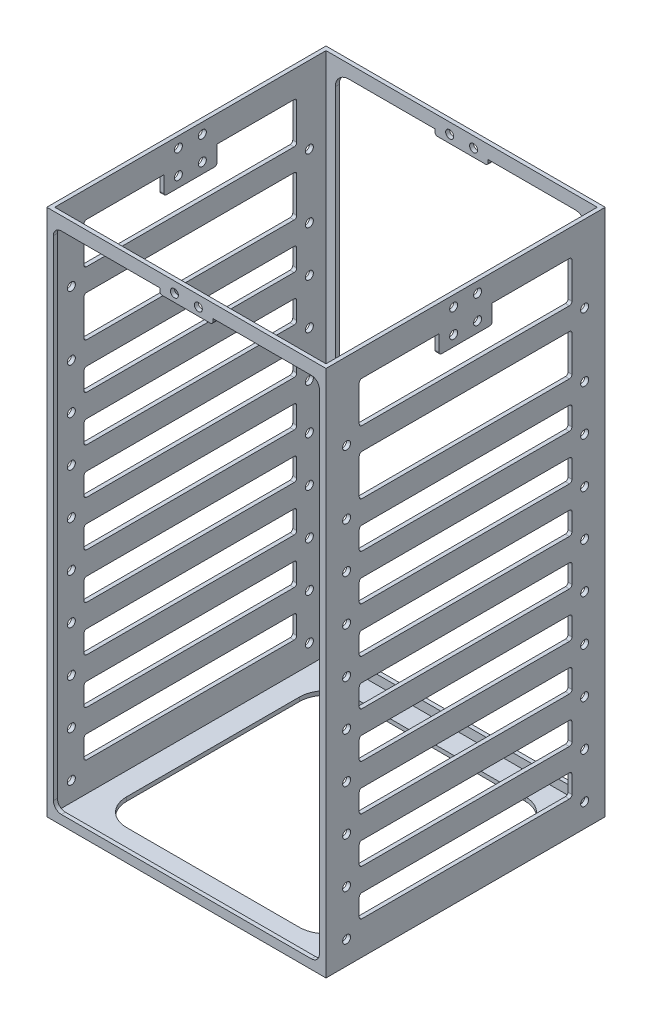
SolidWorks part; units mm, degrees
ref_plane "Front Plane" through (0, 0, 0) normal (0, 0, 1) x (1, 0, 0)
ref_plane "Top Plane" through (0, 0, 0) normal (0, 1, 0) x (1, 0, 0)
ref_plane "Right Plane" through (0, 0, 0) normal (1, 0, 0) x (0, 0, -1)
sketch "Sketch1" plane through (0, 0, 0) normal (0, 1, 0) x (1, 0, 0)
  line L1 (-52.5, -52.5) -> (52.5, -52.5)
  line L2 (-52.5, -52.5) -> (-52.5, 52.5)
  line L3 (-52.5, 52.5) -> (52.5, 52.5)
  line L4 (52.5, -52.5) -> (52.5, 52.5)
  line L5 (-52.5, -52.5) -> (52.5, 52.5) construction
  line L6 (-52.5, 52.5) -> (52.5, -52.5) construction
  line L7 (-32.5, -42.5) -> (32.5, -42.5)
  line L8 (-42.5, -32.5) -> (-42.5, 32.5)
  line L9 (-32.5, 42.5) -> (32.5, 42.5)
  line L10 (42.5, -32.5) -> (42.5, 32.5)
  line L11 (-42.5, -42.5) -> (42.5, 42.5) construction
  line L12 (-42.5, 42.5) -> (42.5, -42.5) construction
  arc A0 (32.5, -42.5) -> (42.5, -32.5) centre (32.5, -32.5) ccw
  arc A1 (32.5, 42.5) -> (42.5, 32.5) centre (32.5, 32.5) cw
  arc A2 (-42.5, 32.5) -> (-32.5, 42.5) centre (-32.5, 32.5) cw
  arc A3 (-32.5, -42.5) -> (-42.5, -32.5) centre (-32.5, -32.5) cw
  point P0 (0, 0)
  point P6 (0, 0)
  dimension "D3" = 10
  dimension "D1" = 105
  dimension "D2" = 42.5
extrude "Boss-Extrude2" add sketch "Sketch1" along normal blind 1.5 contours A3 L7 A0 L10 A1 L9 A2 L8 | L2 L1 L4 L3 region at (0, 0, 0)
sketch "Sketch3" plane through (0, 1.5, 0) normal (0, 1, 0) x (1, 0, 0)
  line L1 (-52.5, -52.5) -> (52.5, -52.5)
  line L2 (-52.5, -52.5) -> (-52.5, 52.5)
  line L3 (-52.5, 52.5) -> (52.5, 52.5)
  line L4 (52.5, -52.5) -> (52.5, 52.5)
  line L5 (-52.5, -52.5) -> (52.5, 52.5) construction
  line L6 (-52.5, 52.5) -> (52.5, -52.5) construction
  line L7 (-51, -51) -> (51, -51)
  line L8 (-51, -51) -> (-51, 51)
  line L9 (-51, 51) -> (51, 51)
  line L10 (51, -51) -> (51, 51)
  line L11 (-51, -51) -> (51, 51) construction
  line L12 (-51, 51) -> (51, -51) construction
  point P0 (0, 0)
  point P7 (0, 0)
  dimension "D1" = 1.5
extrude "Boss-Extrude3" add sketch "Sketch3" along normal blind 197 contours L8 L7 L10 L9 | L2 L3 L4 L1
sketch "Sketch4" plane through (0, 0, -52.5) normal (0, 0, 1) x (1, 0, 0)
  line L0 (-52.5, 0) -> (52.5, 0) construction
  line L1 (-42.5, 5) -> (42.5, 5)
  line L2 (-47.5, 10) -> (-47.5, 188.5)
  line L3 (-42.5, 193.5) -> (42.5, 193.5)
  line L4 (47.5, 10) -> (47.5, 188.5)
  line L5 (-47.5, 5) -> (47.5, 193.5) construction
  line L6 (-47.5, 193.5) -> (47.5, 5) construction
  line L7 (52.5, 198.5) -> (52.5, 0) construction
  line L8 (-51, 198.5) -> (51, 198.5) construction
  line L9 (-52.5, 198.5) -> (-52.5, 0) construction
  arc A0 (-42.5, 5) -> (-47.5, 10) centre (-42.5, 10) cw
  arc A1 (42.5, 5) -> (47.5, 10) centre (42.5, 10) ccw
  arc A2 (42.5, 193.5) -> (47.5, 188.5) centre (42.5, 188.5) cw
  arc A3 (-47.5, 188.5) -> (-42.5, 193.5) centre (-42.5, 188.5) cw
  point P0 (0, 99.25)
  dimension "D5" = 5
  dimension "D1" = 5
  dimension "D2" = 5
  dimension "D3" = 5
  dimension "D4" = 5
extrude "Cut-Extrude1" cut sketch "Sketch4" along normal up to surface (1.5 mm away) up to face at (0, 100, -51)
sketch "Sketch5" plane through (0, 0, 52.5) normal (0, 0, 1) x (1, 0, 0)
  line L0 (-52.5, 198.5) -> (52.5, 198.5) construction
  line L1 (-47, 3.5) -> (47, 3.5)
  line L2 (-50, 6.5) -> (-50, 190.5)
  line L3 (-47, 193.5) -> (47, 193.5)
  line L4 (50, 6.5) -> (50, 190.5)
  line L5 (-50, 3.5) -> (50, 193.5) construction
  line L6 (-50, 193.5) -> (50, 3.5) construction
  line L7 (-52.5, 1.5) -> (52.5, 1.5) construction
  line L8 (-52.5, 198.5) -> (-52.5, 0) construction
  line L9 (52.5, 198.5) -> (52.5, 0) construction
  arc A0 (47, 3.5) -> (50, 6.5) centre (47, 6.5) ccw
  arc A1 (-47, 3.5) -> (-50, 6.5) centre (-47, 6.5) cw
  arc A2 (47, 193.5) -> (50, 190.5) centre (47, 190.5) cw
  arc A3 (-50, 190.5) -> (-47, 193.5) centre (-47, 190.5) cw
  point P0 (0, 98.5)
  dimension "D5" = 3
  dimension "D1" = 5
  dimension "D2" = 2
  dimension "D3" = 2.5
  dimension "D4" = 2.5
sketch "Sketch6" plane through (52.5, 0, 0) normal (1, 0, 0) x (0, 0, -1)
  line L0 (-52.5, 3.5) -> (-52.5, 193.5) construction
  line L1 (52.5, 198.5) -> (52.5, 0) construction
  line L2 (-52.5, 0) -> (52.5, 0) construction
  circle A0 centre (-44.75, 8.75) radius 1.5
  circle A1 centre (44.75, 8.75) radius 1.5
  circle A2 centre (-44.75, 25.85) radius 1.5
  circle A3 centre (44.75, 25.85) radius 1.5
  circle A4 centre (-44.75, 42.95) radius 1.5
  circle A5 centre (44.75, 42.95) radius 1.5
  circle A6 centre (-44.75, 60.05) radius 1.5
  circle A7 centre (44.75, 60.05) radius 1.5
  circle A8 centre (-44.75, 77.15) radius 1.5
  circle A9 centre (44.75, 77.15) radius 1.5
  circle A10 centre (-44.75, 94.25) radius 1.5
  circle A11 centre (44.75, 94.25) radius 1.5
  circle A12 centre (-44.75, 111.35) radius 1.5
  circle A13 centre (44.75, 111.35) radius 1.5
  circle A14 centre (-44.75, 128.45) radius 1.5
  circle A15 centre (44.75, 128.45) radius 1.5
  circle A16 centre (-44.75, 145.55) radius 1.5
  circle A17 centre (44.75, 145.55) radius 1.5
  circle A18 centre (-44.75, 169.55) radius 1.5
  circle A19 centre (44.75, 169.55) radius 1.5
  dimension "D4" = 3
  dimension "D5" = 3
  dimension "D1" = 7.75
  dimension "D2" = 7.75
  dimension "D3" = 8.75
  dimension "D7" = 17.1
  dimension "D9" = 24
  dimension "D6" = 9
  dimension "D8" = 2
extrude "Cut-Extrude2" cut sketch "Sketch6" against normal through all
extrude "Cut-Extrude3" cut sketch "Sketch5" against normal up to surface (1.5 mm away) up to face at (0, 100, 51)
sketch "Sketch7" plane through (52.5, 0, 0) normal (1, 0, 0) x (0, 0, -1)
  line L0 (-40, 30.65) -> (-40, 37.15)
  line L1 (-39, 12.55) -> (39, 12.55)
  line L2 (-40, 13.55) -> (-40, 20.05)
  line L3 (-39, 21.05) -> (39, 21.05)
  line L4 (40, 13.55) -> (40, 20.05)
  line L5 (-40, 12.55) -> (40, 21.05) construction
  line L6 (-40, 21.05) -> (40, 12.55) construction
  line L7 (52.5, 198.5) -> (52.5, 0) construction
  line L8 (-39, 29.65) -> (39, 29.65)
  line L9 (40, 30.65) -> (40, 37.15)
  line L10 (-39, 38.15) -> (39, 38.15)
  line L11 (-40, 47.75) -> (-40, 54.25)
  line L12 (-39, 46.75) -> (39, 46.75)
  line L13 (40, 47.75) -> (40, 54.25)
  line L14 (-39, 55.25) -> (39, 55.25)
  line L15 (-40, 64.85) -> (-40, 71.35)
  line L16 (-39, 63.85) -> (39, 63.85)
  line L17 (40, 64.85) -> (40, 71.35)
  line L18 (-39, 72.35) -> (39, 72.35)
  line L19 (-40, 81.95) -> (-40, 88.45)
  line L20 (-39, 80.95) -> (39, 80.95)
  line L21 (40, 81.95) -> (40, 88.45)
  line L22 (-39, 89.45) -> (39, 89.45)
  line L23 (-40, 99.05) -> (-40, 105.55)
  line L24 (-39, 98.05) -> (39, 98.05)
  line L25 (40, 99.05) -> (40, 105.55)
  line L26 (-39, 106.55) -> (39, 106.55)
  line L27 (-40, 116.15) -> (-40, 122.65)
  line L28 (-39, 115.15) -> (39, 115.15)
  line L29 (40, 116.15) -> (40, 122.65)
  line L30 (-39, 123.65) -> (39, 123.65)
  line L31 (-40, 133.25) -> (-40, 139.75)
  line L32 (-39, 132.25) -> (39, 132.25)
  line L33 (40, 133.25) -> (40, 139.75)
  line L34 (-39, 140.75) -> (39, 140.75)
  circle A0 centre (-44.75, 8.75) radius 1.5 construction
  arc A1 (39, 21.05) -> (40, 20.05) centre (39, 20.05) cw
  arc A2 (39, 12.55) -> (40, 13.55) centre (39, 13.55) ccw
  arc A3 (-39, 12.55) -> (-40, 13.55) centre (-39, 13.55) cw
  arc A4 (-40, 20.05) -> (-39, 21.05) centre (-39, 20.05) cw
  arc A5 (-40, 37.15) -> (-39, 38.15) centre (-39, 37.15) cw
  arc A6 (-39, 29.65) -> (-40, 30.65) centre (-39, 30.65) cw
  arc A7 (39, 29.65) -> (40, 30.65) centre (39, 30.65) ccw
  arc A8 (39, 38.15) -> (40, 37.15) centre (39, 37.15) cw
  arc A9 (-40, 54.25) -> (-39, 55.25) centre (-39, 54.25) cw
  arc A10 (-39, 46.75) -> (-40, 47.75) centre (-39, 47.75) cw
  arc A11 (39, 46.75) -> (40, 47.75) centre (39, 47.75) ccw
  arc A12 (39, 55.25) -> (40, 54.25) centre (39, 54.25) cw
  arc A13 (-40, 71.35) -> (-39, 72.35) centre (-39, 71.35) cw
  arc A14 (-39, 63.85) -> (-40, 64.85) centre (-39, 64.85) cw
  arc A15 (39, 63.85) -> (40, 64.85) centre (39, 64.85) ccw
  arc A16 (39, 72.35) -> (40, 71.35) centre (39, 71.35) cw
  arc A17 (-40, 88.45) -> (-39, 89.45) centre (-39, 88.45) cw
  arc A18 (-39, 80.95) -> (-40, 81.95) centre (-39, 81.95) cw
  arc A19 (39, 80.95) -> (40, 81.95) centre (39, 81.95) ccw
  arc A20 (39, 89.45) -> (40, 88.45) centre (39, 88.45) cw
  arc A21 (-40, 105.55) -> (-39, 106.55) centre (-39, 105.55) cw
  arc A22 (-39, 98.05) -> (-40, 99.05) centre (-39, 99.05) cw
  arc A23 (39, 98.05) -> (40, 99.05) centre (39, 99.05) ccw
  arc A24 (39, 106.55) -> (40, 105.55) centre (39, 105.55) cw
  arc A25 (-40, 122.65) -> (-39, 123.65) centre (-39, 122.65) cw
  arc A26 (-39, 115.15) -> (-40, 116.15) centre (-39, 116.15) cw
  arc A27 (39, 115.15) -> (40, 116.15) centre (39, 116.15) ccw
  arc A28 (39, 123.65) -> (40, 122.65) centre (39, 122.65) cw
  arc A29 (-40, 139.75) -> (-39, 140.75) centre (-39, 139.75) cw
  arc A30 (-39, 132.25) -> (-40, 133.25) centre (-39, 133.25) cw
  arc A31 (39, 132.25) -> (40, 133.25) centre (39, 133.25) ccw
  arc A32 (39, 140.75) -> (40, 139.75) centre (39, 139.75) cw
  point P0 (0, 16.8)
  dimension "D5" = 1
  dimension "D1" = 8.5
  dimension "D2" = 3.8
  dimension "D3" = 80
  dimension "D4" = 12.5
  dimension "D7" = 8.6
  dimension "D6" = 8
extrude "Cut-Extrude4" cut sketch "Sketch7" against normal through all
sketch "Sketch8" plane through (52.5, 0, 0) normal (1, 0, 0) x (0, 0, -1)
  line L1 (-39, 149.35) -> (39, 149.35)
  line L2 (-40, 150.35) -> (-40, 163.75)
  line L3 (-39, 164.75) -> (39, 164.75)
  line L4 (40, 150.35) -> (40, 163.75)
  line L5 (-40, 149.35) -> (40, 164.75) construction
  line L6 (-40, 164.75) -> (40, 149.35) construction
  line L7 (52.5, 198.5) -> (52.5, 0) construction
  line L8 (-40, 188.55) -> (40, 173.15) construction
  line L9 (-40, 174.15) -> (-40, 187.55)
  line L10 (-39, 173.15) -> (39, 173.15)
  line L11 (40, 174.15) -> (40, 187.55)
  line L12 (-39, 188.55) -> (39, 188.55)
  circle A0 centre (-44.75, 145.55) radius 1.5 construction
  arc A2 (-40, 163.75) -> (-39, 164.75) centre (-39, 163.75) cw
  arc A3 (39, 164.75) -> (40, 163.75) centre (39, 163.75) cw
  arc A4 (39, 149.35) -> (40, 150.35) centre (39, 150.35) ccw
  arc A5 (-39, 149.35) -> (-40, 150.35) centre (-39, 150.35) cw
  arc A6 (-39, 173.15) -> (-40, 174.15) centre (-39, 174.15) cw
  arc A7 (-40, 187.55) -> (-39, 188.55) centre (-39, 187.55) cw
  arc A8 (39, 173.15) -> (40, 174.15) centre (39, 174.15) ccw
  arc A9 (39, 188.55) -> (40, 187.55) centre (39, 187.55) cw
  point P0 (0, 157.05)
  dimension "D5" = 1
  dimension "D1" = 3.8
  dimension "D2" = 15.4
  dimension "D3" = 80
  dimension "D4" = 12.5
  dimension "D7" = 8.4
  dimension "D6" = 2
extrude "Cut-Extrude5" cut sketch "Sketch8" against normal through all
sketch "Sketch15" plane through (52.5, 0, 0) normal (1, 0, 0) x (0, 0, -1)
  line L0 (39, 188.55) -> (-39, 188.55) construction
  line L1 (-10, 188.55) -> (10, 188.55)
  line L2 (-10, 188.55) -> (-10, 182.55)
  line L3 (-9, 181.55) -> (9, 181.55)
  line L4 (10, 188.55) -> (10, 182.55)
  line L5 (-52.5, 198.5) -> (-52.5, 0) construction
  arc A0 (9, 181.55) -> (10, 182.55) centre (9, 182.55) ccw
  arc A1 (-10, 182.55) -> (-9, 181.55) centre (-9, 182.55) ccw
  dimension "D4" = 1
  dimension "D1" = 20
  dimension "D2" = 7
  dimension "D3" = 42.5
extrude "Boss-Extrude4" add sketch "Sketch15" against normal up to surface (1.5 mm away) up to face at (51, 157.05, 0)
sketch "Sketch16" plane through (-52.5, 0, 0) normal (-1, 0, 0) x (0, 0, 1)
  line L1 (-10, 188.55) -> (10, 188.55)
  line L2 (-10, 188.55) -> (-10, 182.55)
  line L3 (-9, 181.55) -> (9, 181.55)
  line L4 (10, 188.55) -> (10, 182.55)
  arc A0 (9, 181.55) -> (10, 182.55) centre (9, 182.55) ccw
  arc A1 (-10, 182.55) -> (-9, 181.55) centre (-9, 182.55) ccw
  dimension "D3" = 1
  dimension "D1" = 7
  dimension "D2" = 20
extrude "Boss-Extrude5" add sketch "Sketch16" against normal up to surface (1.5 mm away) up to face at (-51, 157.05, 0)
sketch "Sketch9" plane through (52.5, 0, 0) normal (1, 0, 0) x (0, 0, -1)
  line L0 (-52.5, 198.5) -> (52.5, 198.5) construction
  line L1 (-52.5, 198.5) -> (-52.5, 0) construction
  line L2 (-10.0428, 190) -> (10.2919, 190) construction
  circle A0 centre (-4.5, 194.5) radius 1.5
  circle A1 centre (4.5, 194.5) radius 1.5
  circle A2 centre (4.5, 185.5) radius 1.5
  circle A3 centre (-4.5, 185.5) radius 1.5
  dimension "D1" = 3
  dimension "D3" = 9
  dimension "D5" = 3
  dimension "D2" = 4
  dimension "D4" = 48
  dimension "D6" = 4.5
extrude "Cut-Extrude6" cut sketch "Sketch9" against normal through all
sketch "Sketch17" plane through (0, 0, 52.5) normal (0, 0, 1) x (1, 0, 0)
  line L0 (47, 193.5) -> (-47, 193.5) construction
  line L1 (-10, 193.5) -> (10, 193.5)
  line L2 (-10, 193.5) -> (-10, 192.5)
  line L3 (-9, 191.5) -> (9, 191.5)
  line L4 (10, 193.5) -> (10, 192.5)
  line L5 (-52.5, 198.5) -> (-52.5, 0) construction
  arc A0 (9, 191.5) -> (10, 192.5) centre (9, 192.5) ccw
  arc A1 (-10, 192.5) -> (-9, 191.5) centre (-9, 192.5) ccw
  dimension "D4" = 1
  dimension "D1" = 20
  dimension "D2" = 42.5
  dimension "D3" = 2
extrude "Boss-Extrude6" add sketch "Sketch17" against normal up to surface (1.5 mm away) up to face at (0, 98.5, 51)
sketch "Sketch18" plane through (0, 0, -52.5) normal (0, 0, -1) x (-1, 0, 0)
  line L1 (-10, 193.5) -> (10, 193.5)
  line L2 (-10, 193.5) -> (-10, 192.5)
  line L3 (-9, 191.5) -> (9, 191.5)
  line L4 (10, 193.5) -> (10, 192.5)
  arc A0 (9, 191.5) -> (10, 192.5) centre (9, 192.5) ccw
  arc A1 (-10, 192.5) -> (-9, 191.5) centre (-9, 192.5) ccw
  dimension "D3" = 1
  dimension "D1" = 2
  dimension "D2" = 20
extrude "Boss-Extrude7" add sketch "Sketch18" against normal up to surface (1.5 mm away) up to face at (0, 99.25, -51)
sketch "Sketch19" plane through (0, 0, 52.5) normal (0, 0, 1) x (1, 0, 0)
  line L0 (0, 198.5) -> (0, 191.5) construction
  line L1 (-9, 191.5) -> (9, 191.5) construction
  line L3 (-52.5, 198.5) -> (52.5, 198.5) construction
  circle A0 centre (-4.5, 194.5) radius 1.5
  circle A1 centre (4.5, 194.5) radius 1.5
  dimension "D1" = 3
  dimension "D2" = 4
  dimension "D3" = 4.5
extrude "Cut-Extrude7" cut sketch "Sketch19" against normal through all
